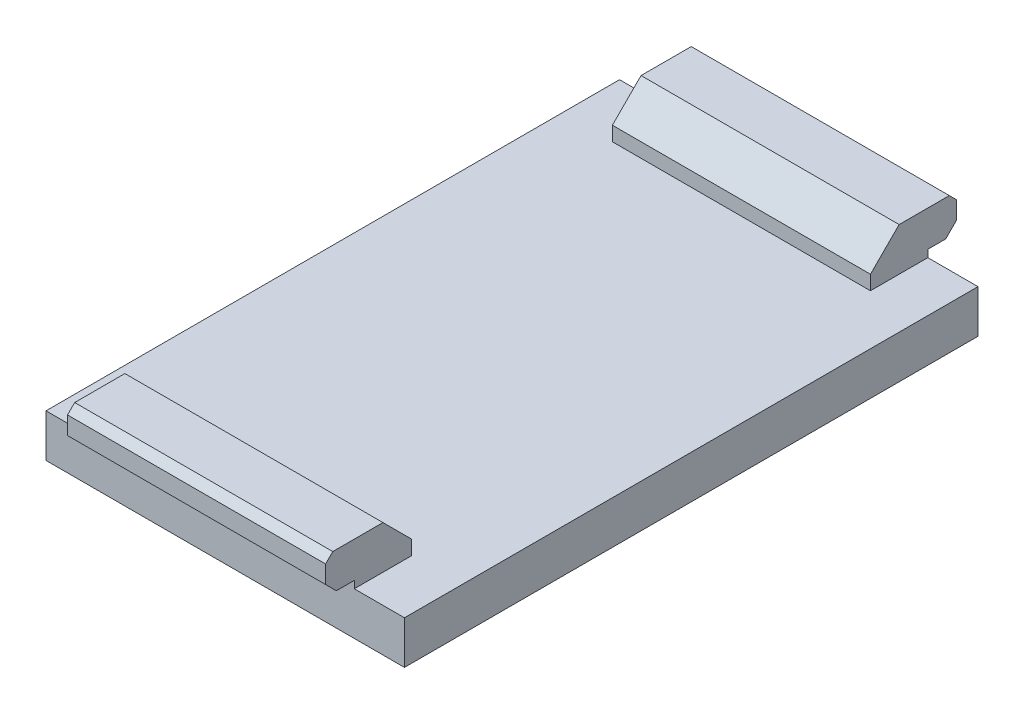
SolidWorks part; units mm, degrees
ref_plane "Front" through (0, 0, 0) normal (0, 0, 1) x (1, 0, 0)
ref_plane "Top" through (0, 0, 0) normal (0, 1, 0) x (1, 0, 0)
ref_plane "Right" through (0, 0, 0) normal (1, 0, 0) x (0, 0, -1)
sketch "Эскиз1" plane through (0, 0, 0) normal (0, 0, 1) x (1, 0, 0)
  line L1 (-17.0795, 18.39) -> (7.9205, 18.39)
  line L2 (-17.0795, 18.39) -> (-17.0795, 15.39)
  line L3 (-17.0795, 15.39) -> (7.9205, 15.39)
  line L4 (7.9205, 18.39) -> (7.9205, 15.39)
  dimension "D1" = 3
  dimension "D2" = 25
extrude "Бобышка-Вытянуть1" add sketch "Эскиз1" along normal blind 20
sketch "Эскиз2" plane through (0, 18.39, 0) normal (0, 1, 0) x (1, 0, 0)
  line L0 (7.9205, 0) -> (-17.0795, 0) construction
  line L1 (-13.5795, 0) -> (4.4205, 0)
  line L2 (-13.5795, 0) -> (-13.5795, -4)
  line L3 (-13.5795, -4) -> (4.4205, -4)
  line L4 (4.4205, 0) -> (4.4205, -4)
  line L5 (7.9205, -20) -> (7.9205, 0) construction
  line L6 (-17.0795, -20) -> (-17.0795, 0) construction
  dimension "D1" = 3.5
  dimension "D2" = 3.5
  dimension "D3" = 4
extrude "Бобышка-Вытянуть2" add sketch "Эскиз2" along normal blind 3
sketch "Эскиз3" plane through (0, 0, 0) normal (0, 0, -1) x (-1, 0, 0)
  line L0 (13.5795, 21.39) -> (13.5795, 18.39) construction
  line L1 (-4.4205, 21.39) -> (13.5795, 21.39)
  line L2 (-4.4205, 21.39) -> (-4.4205, 19.89)
  line L4 (13.5795, 21.39) -> (13.5795, 19.89)
  line L5 (-4.4205, 19.89) -> (-4.4205, 18.8965)
  line L6 (-4.4205, 21.39) -> (-4.4205, 18.39) construction
  line L7 (-4.4205, 18.8965) -> (13.5795, 18.8965)
  line L8 (13.5795, 18.8965) -> (13.5795, 19.89)
extrude "Бобышка-Вытянуть3" add sketch "Эскиз3" along normal blind 2
chamfer "Фаска1" distance 0.75 angle 45 1 edges at (-4.5795, 18.8965, -2)
chamfer "Фаска2" distance 0.5 angle 45 1 edges at (-4.5795, 21.39, -2)
chamfer "Фаска3" distance 2 angle 45 1 edges at (-4.5795, 21.39, 4)
mirror "Зеркальное отражение1" about plane through (0, 0, 20) normal (0, 0, 1) of bodies 103
